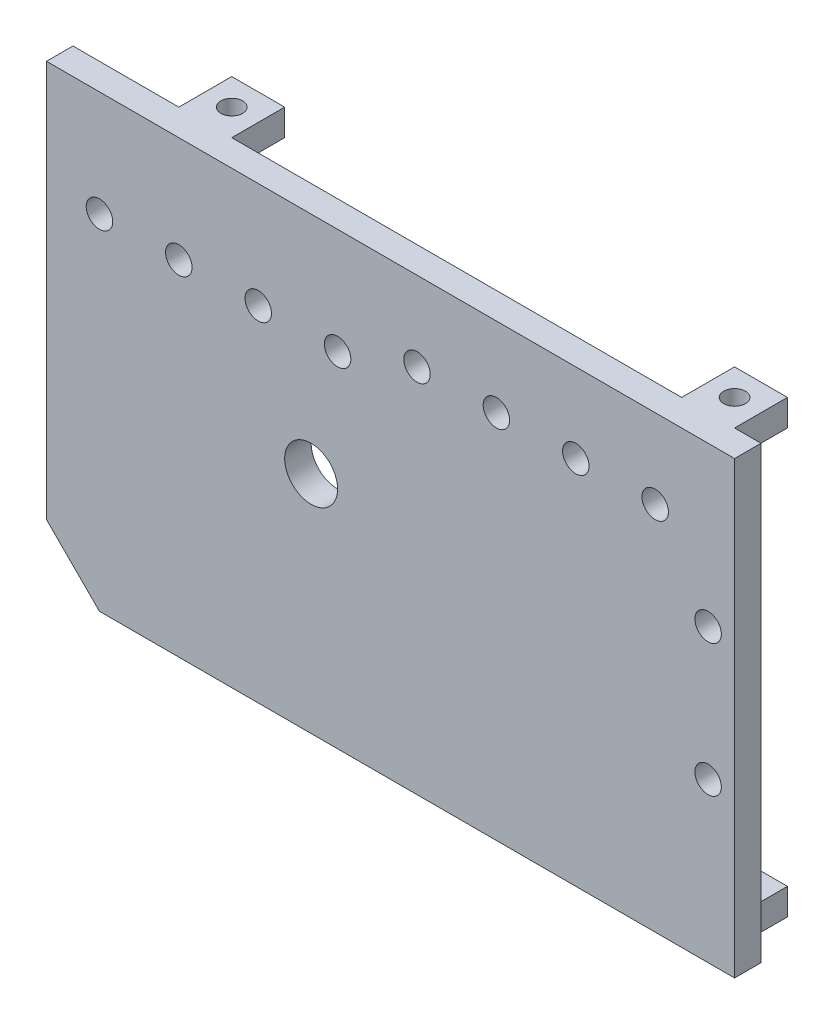
SolidWorks part; units mm, degrees
material "PLA+ esun"
ref_plane "Front Plane" through (0, 0, 0) normal (0, 0, 1) x (1, 0, 0)
ref_plane "Top Plane" through (0, 0, 0) normal (0, 1, 0) x (1, 0, 0)
ref_plane "Right Plane" through (0, 0, 0) normal (1, 0, 0) x (0, 0, -1)
sketch "Sketch1" plane through (0, 0, 0) normal (0, 0, 1) x (1, 0, 0)
  line L1 (-80, 42.5) -> (80, 42.5)
  line L2 (-80, 42.5) -> (-80, -42.5)
  line L3 (-80, -42.5) -> (80, -42.5)
  line L4 (80, 42.5) -> (80, -42.5)
  line L5 (-80, 42.5) -> (80, -42.5) construction
  line L6 (-80, -42.5) -> (80, 42.5) construction
  circle A0 centre (0, 0) radius 5
  point P0 (0, 0)
  dimension "D3" = 10
  dimension "D1" = 85
  dimension "D2" = 160
extrude "Boss-Extrude1" add sketch "Sketch1" along normal blind 5
sketch "Sketch3" plane through (0, 0, 5) normal (0, 0, 1) x (1, 0, 0)
  line L0 (-80, -42.5) -> (80, -42.5) construction
  line L1 (-80, 42.5) -> (-50, 42.5)
  line L2 (-80, 42.5) -> (-80, -42.5)
  line L3 (-80, -42.5) -> (-50, -42.5)
  line L4 (-50, 42.5) -> (-50, -42.5)
  dimension "D1" = 30
extrude "Cut-Extrude2" cut sketch "Sketch3" against normal blind 15
sketch "Sketch5" plane through (0, 0, 5) normal (0, 0, 1) x (1, 0, 0)
  line L0 (80, 42.5) -> (-50, 42.5) construction
  line L2 (80, -42.5) -> (80, 42.5) construction
  circle A0 centre (65, 27.5) radius 2.5
  circle A1 centre (50, 27.5) radius 2.5
  circle A2 centre (35, 27.5) radius 2.5
  circle A3 centre (20, 27.5) radius 2.5
  circle A8 centre (-40, 27.5) radius 2.5 [skipped]
  circle A9 centre (-25, 27.5) radius 2.5 [skipped]
  circle A10 centre (-10, 27.5) radius 2.5 [skipped]
  circle A11 centre (5, 27.5) radius 2.5 [skipped]
  circle A12 centre (5, 22.5) radius 2.5
  circle A13 centre (-10, 22.5) radius 2.5
  circle A14 centre (-25, 22.5) radius 2.5
  circle A15 centre (-40, 22.5) radius 2.5
  dimension "D1" = 5
  dimension "D2" = 15
  dimension "D3" = 15
  dimension "D5" = 15
  dimension "D6" = 5
  dimension "D7" = 15
  dimension "D8" = 20
  dimension "D4" = 8
  dimension "D9" = 4
extrude "Cut-Extrude3" cut sketch "Sketch5" against normal blind 15
chamfer "Chamfer1" distance 10 angle 45 1 edges at (-50, -42.5, 2.5)
sketch "Sketch6" plane through (0, 0, 0) normal (0, 0, -1) x (-1, 0, 0)
  line L0 (40, -42.5) -> (-80, -42.5) construction
  line L1 (-80, -42.5) -> (-75, -42.5)
  line L2 (-80, -42.5) -> (-80, -37.5)
  line L3 (-80, -37.5) -> (-75, -37.5)
  line L4 (-75, -42.5) -> (-75, -37.5)
  line L5 (-75, -37.5) -> (-65, -37.5)
  line L6 (-75, -37.5) -> (-75, -42.5)
  line L7 (-75, -42.5) -> (-65, -42.5)
  line L8 (-65, -37.5) -> (-65, -42.5)
  line L15 (50, -32.5) -> (50, 42.5) construction
  line L16 (30, -42.5) -> (20, -42.5)
  line L17 (30, -42.5) -> (30, -37.5)
  line L18 (30, -37.5) -> (20, -37.5)
  line L19 (20, -42.5) -> (20, -37.5)
  line M14 (-80, -42.5) -> (40, -42.5)
  dimension "D1" = 5
  dimension "D2" = 5
  dimension "D3" = 10
  dimension "D4" = 5
  dimension "D5" = 10
  dimension "D6" = 20
extrude "Boss-Extrude2" add sketch "Sketch6" along normal blind 10 contours L8 L5 L4 M14 | L19 L17 L18 M14 region at (-25, -40, 0) region at (70, -40, 0)
sketch "Sketch7" plane through (0, -37.5, 0) normal (0, 1, 0) x (1, 0, 0)
  line L0 (75, 10) -> (65, 10) construction
  line L1 (65, 10) -> (65, 0) construction
  line L2 (-30, 10) -> (-20, 10) construction
  line L3 (-20, 10) -> (-20, 0) construction
  circle A0 centre (70, 5) radius 2.05
  circle A1 centre (-25, 5) radius 2.05
  dimension "D1" = 5
  dimension "D2" = 5
  dimension "D3" = 5
  dimension "D4" = 4.1
  dimension "D5" = 5
  dimension "D6" = 4.1
extrude "Cut-Extrude4" cut sketch "Sketch7" against normal through all
ref_plane "Plane1" through (0, 0, 0) normal (0, 1, 0) x (1, 0, 0)
mirror "Mirror1" about plane through (0, 0, 0) normal (0, 1, 0) of "Boss-Extrude2"
mirror "Mirror2" about plane through (0, 0, 0) normal (0, 1, 0) of "Cut-Extrude4"
sketch "Sketch8" plane through (0, 0, 5) normal (0, 0, 1) x (1, 0, 0)
  line L0 (80, 42.5) -> (-50, 42.5) construction
  line L1 (80, -42.5) -> (80, 42.5) construction
  circle A0 centre (75, 12.5) radius 2.5
  circle A2 centre (75, -12.5) radius 2.5
  dimension "D1" = 5
  dimension "D2" = 30
  dimension "D3" = 5
  dimension "D5" = 25
  dimension "D4" = 2
extrude "Cut-Extrude5" cut sketch "Sketch8" against normal through all
